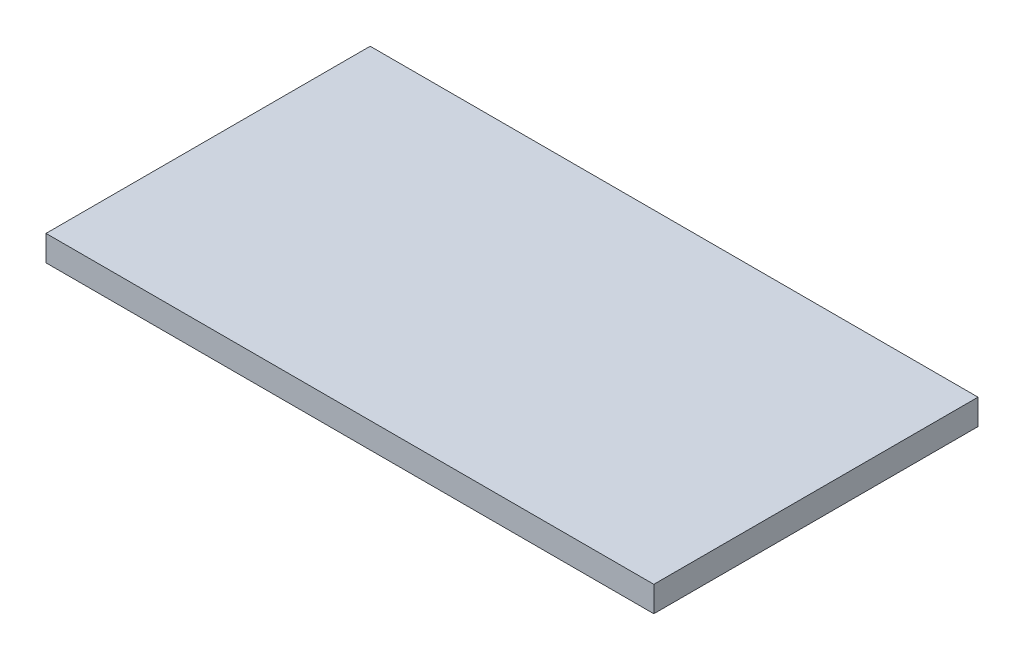
SolidWorks part; units mm, degrees
ref_plane "Front Plane" through (0, 0, 0) normal (0, 0, 1) x (1, 0, 0)
ref_plane "Top Plane" through (0, 0, 0) normal (0, 1, 0) x (1, 0, 0)
ref_plane "Right Plane" through (0, 0, 0) normal (1, 0, 0) x (0, 0, -1)
sketch "Sketch1" plane through (0, 0, 0) normal (0, 1, 0) x (1, 0, 0)
  line L1 (-19.05, -10.16) -> (19.05, -10.16)
  line L2 (-19.05, -10.16) -> (-19.05, 10.16)
  line L3 (-19.05, 10.16) -> (19.05, 10.16)
  line L4 (19.05, -10.16) -> (19.05, 10.16)
  line L5 (-19.05, -10.16) -> (19.05, 10.16) construction
  line L6 (-19.05, 10.16) -> (19.05, -10.16) construction
  point P0 (0, 0)
  dimension "D1" = 20.32
  dimension "D2" = 38.1
extrude "Boss-Extrude1" add sketch "Sketch1" along normal mid plane 1.6
